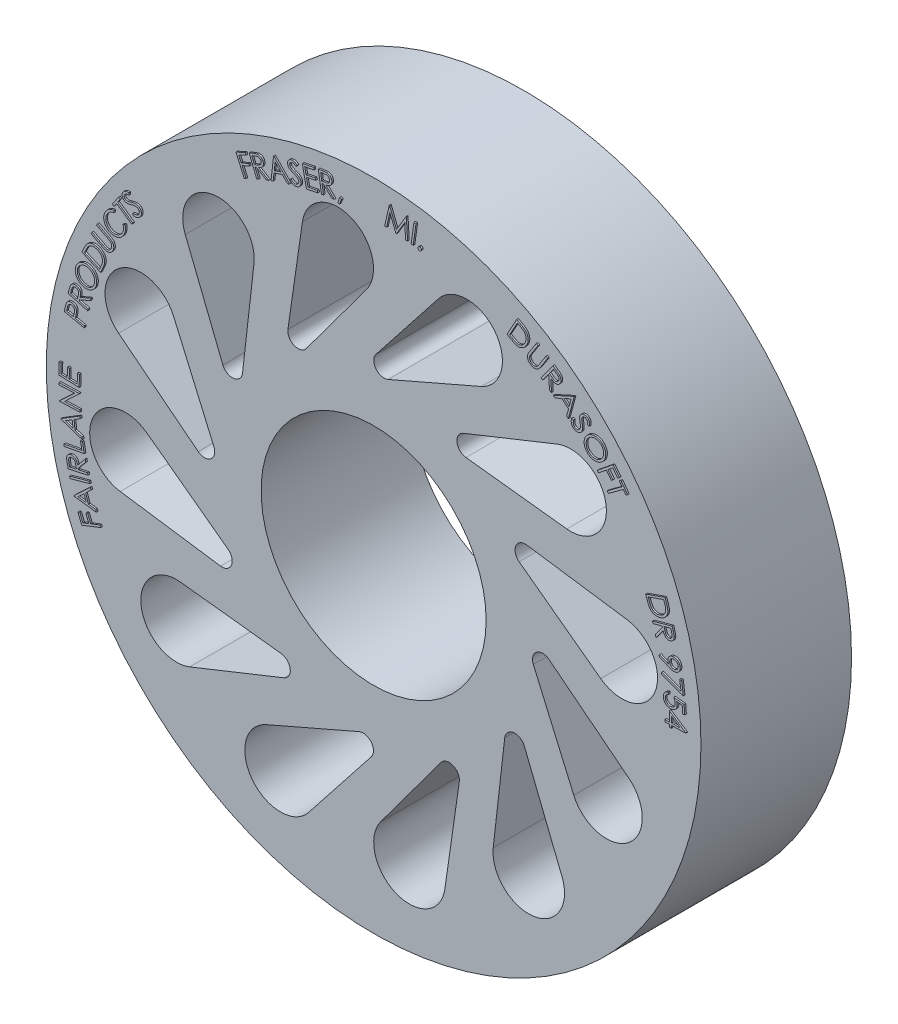
SolidWorks part; units mm, degrees
ref_plane "Front" through (0, 0, 0) normal (0, 0, 1) x (1, 0, 0)
ref_plane "Top" through (0, 0, 0) normal (0, 1, 0) x (1, 0, 0)
ref_plane "Right" through (0, 0, 0) normal (1, 0, 0) x (0, 0, -1)
sketch "Sketch1" plane through (0, 0, 0) normal (0, 0, 1) x (1, 0, 0)
  circle A0 centre (0, 0) radius 50.8
  dimension "D1" = 101.6
extrude "Base-Extrude" add sketch "Sketch1" along normal blind 23.368
sketch "Sketch2" plane through (0, 0, 23.368) normal (0, 0, 1) x (1, 0, 0)
  circle A0 centre (0, 0) radius 17.4625
  dimension "D1" = 34.925
extrude "Cut-Extrude1" cut sketch "Sketch2" against normal through all
sketch "Sketch3" plane through (0, 0, 23.368) normal (0, 0, 1) x (1, 0, 0)
  circle A0 centre (0, 0) radius 48.641 construction
  circle A1 centre (0, 0) radius 45.466 construction
  text T0 "FAIRLANE     PRODUCTS                FRASER,     MI.           DURASOFT         DR 9754"
  dimension "D1" = 97.282
  dimension "D2" = 90.932
sketch "Sketch4" plane through (0, 0, 23.368) normal (0, 0, 1) x (1, 0, 0)
  line L0 (0, 0) -> (0, -45.5795) construction
  line L1 (0, 0) -> (23.0118, -39.8576) construction
  line L3 (13.2978, -23.7512) -> (11.0516, -39.3237)
  line L4 (10.4577, -22.5786) -> (1.0839, -35.2425)
  arc A0 (13.2978, -23.7512) -> (10.4577, -22.5786) centre (11.7252, -23.5344) ccw
  circle A3 centre (0, 0) radius 44.45 construction
  arc A5 (1.0839, -35.2425) -> (11.0516, -39.3237) centre (5.5626, -38.5168) ccw
  dimension "D5" = 1.5875
  dimension "D2" = 5.5626
  dimension "D3" = 30
  dimension "D1" = 1.6129
extrude "Cut-Extrude2" cut sketch "Sketch4" against normal through all
pattern_circular "CirPattern1" count 12 every 30 about axis through (0, 0, 0) along (0, 0, -1) of "Cut-Extrude2"
extrude "Boss-Extrude1" add sketch "Sketch3" along normal blind 0.254
